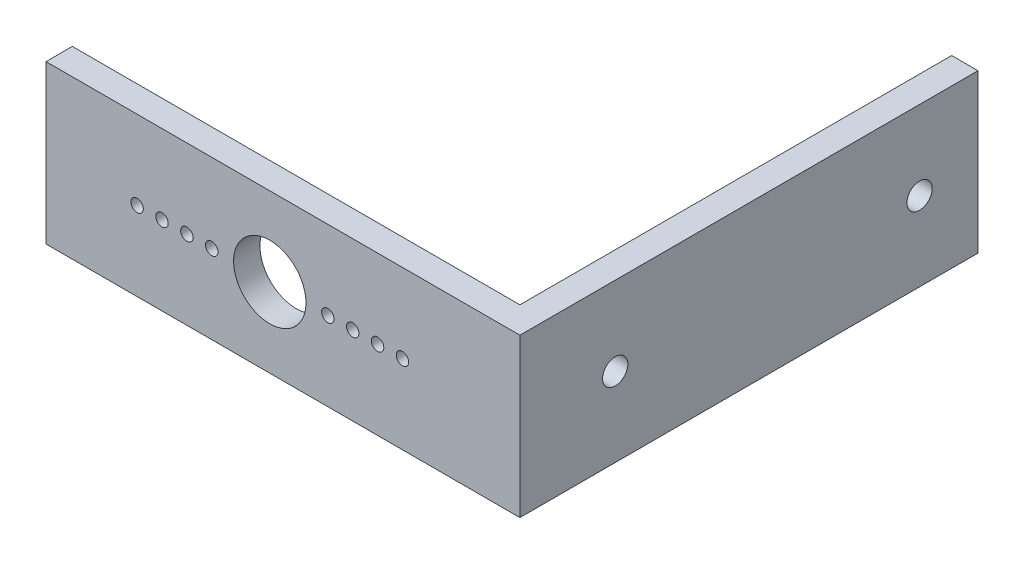
SolidWorks part; units mm, degrees
ref_plane "Front" through (0, 0, 0) normal (0, 0, 1) x (1, 0, 0)
ref_plane "Top" through (0, 0, 0) normal (0, 1, 0) x (1, 0, 0)
ref_plane "Right" through (0, 0, 0) normal (1, 0, 0) x (0, 0, -1)
sketch "Sketch1" plane through (0, 0, 0) normal (0, 0, 1) x (1, 0, 0)
  line L0 (26.9875, 19.05) -> (26.9875, 0) construction
  line L1 (0, 0) -> (53.975, 0)
  line L2 (0, 0) -> (0, 19.05)
  line L3 (0, 19.05) -> (53.975, 19.05)
  line L4 (53.975, 0) -> (53.975, 19.05)
  line L5 (0, 9.525) -> (53.975, 9.525) construction
  circle A0 centre (33.9875, 9.525) radius 0.75
  circle A1 centre (42.9875, 9.525) radius 0.75
  circle A2 centre (36.9875, 9.525) radius 0.75
  circle A3 centre (39.9875, 9.525) radius 0.75
  circle A4 centre (19.9875, 9.525) radius 0.75
  circle A5 centre (16.9875, 9.525) radius 0.75
  circle A6 centre (13.9875, 9.525) radius 0.75
  circle A7 centre (10.9875, 9.525) radius 0.75
  circle A8 centre (26.9875, 9.525) radius 4.3656
  point P19 (26.9875, 9.525)
  point P44 (26.9875, 9.525)
  dimension "D7" = 1.5
  dimension "D9" = 8.7312
  dimension "D1" = 53.975
  dimension "D2" = 19.05
  dimension "D3" = 7
  dimension "D4" = 10
  dimension "D5" = 13
  dimension "D6" = 16
  dimension "D8" = 2
extrude "Boss-Extrude1" add sketch "Sketch1" along normal blind 3.175
sketch "Sketch2" plane through (53.975, 0, 0) normal (1, 0, 0) x (0, 0, -1)
  line L0 (-3.175, 19.05) -> (0, 19.05) construction
  line L1 (-3.175, 0) -> (52.07, 0)
  line L2 (-3.175, 0) -> (-3.175, 19.05)
  line L3 (-3.175, 19.05) -> (52.07, 19.05)
  line L4 (52.07, 0) -> (52.07, 19.05)
  line L5 (8.3185, 9.525) -> (45.0215, 9.525) construction
  circle A0 centre (8.3185, 9.525) radius 1.524
  circle A1 centre (45.0215, 9.525) radius 1.524
  point P7 (26.67, 9.525)
  point P8 (52.07, 9.525)
  dimension "D3" = 3.048
  dimension "D1" = 55.245
  dimension "D2" = 36.703
  dimension "D4" = 25.4
extrude "Boss-Extrude2" add sketch "Sketch2" along normal blind 3.175
